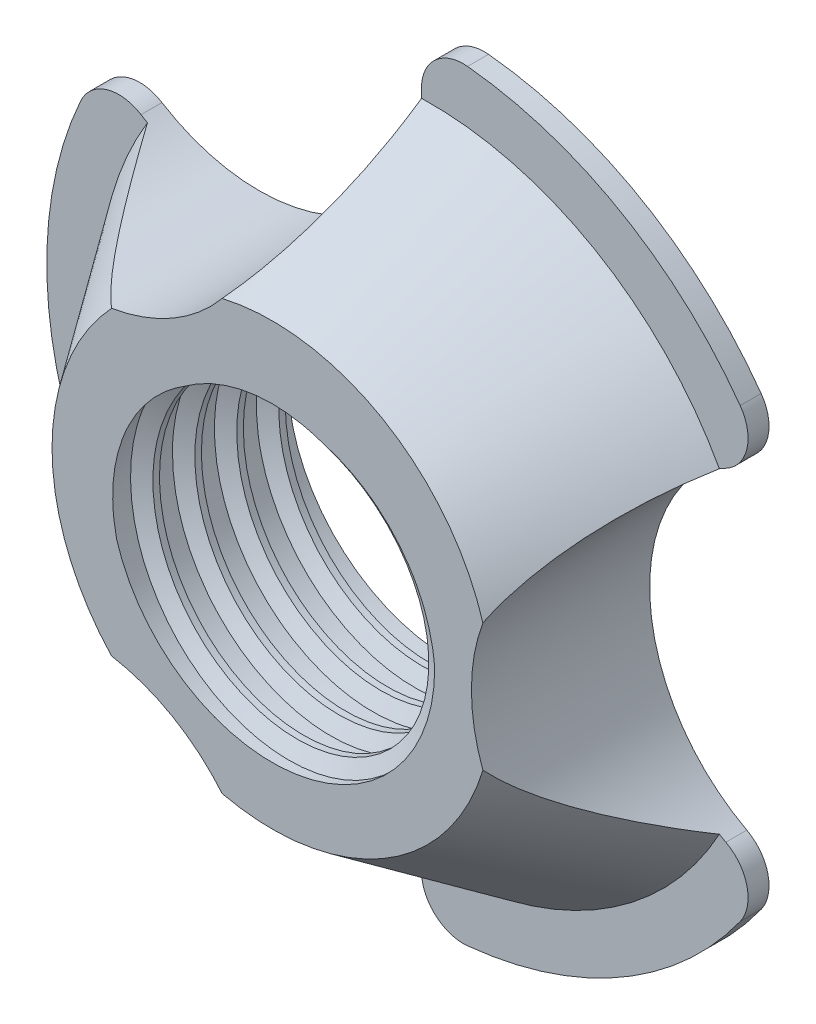
SolidWorks part; units mm, degrees
ref_plane "Спереди" through (0, 0, 0) normal (0, 0, 1) x (1, 0, 0)
ref_plane "Сверху" through (0, 0, 0) normal (0, 1, 0) x (1, 0, 0)
ref_plane "Справа" through (0, 0, 0) normal (1, 0, 0) x (0, 0, -1)
sketch "Эскиз2" plane through (0, 0, 0) normal (0, 0, 1) x (1, 0, 0)
  circle A2 centre (0, 0) radius 21
  dimension "D1" = 42
extrude "Бобышка-Вытянуть2" add sketch "Эскиз2" against normal blind 15 draft 35 separate body draft outward yes
sketch "Эскиз6" plane through (0, 0, -15) normal (0, 0, -1) x (-1, 0, 0)
  circle A0 centre (0, 0) radius 31.5031 construction
  circle A2 centre (0, 0) radius 36.5031
  dimension "D1" = 5
extrude "Бобышка-Вытянуть3" add sketch "Эскиз6" along normal blind 2
sketch "Эскиз7" plane through (0, 0, -17) normal (0, 0, -1) x (-1, 0, 0)
  circle A1 centre (0, 0) radius 31.5031 construction
  circle A2 centre (0, 0) radius 31.5031 construction
  circle A3 centre (-36.5031, 0) radius 17.5
  circle A4 centre (18.2516, 31.6126) radius 17.5
  circle A5 centre (18.2516, -31.6126) radius 17.5
  circle A6 centre (0, 0) radius 36.5031 construction
  point P12 (0, 0)
  dimension "D1" = 35
  dimension "D2" = 3
extrude "Вырез-Вытянуть1" cut sketch "Эскиз7" against normal through all
fillet "Скругление1" radius 4 6 edges at (32.3083, -16.9898, -16) (-1.4405, -36.4747, -16) (-30.8677, -19.4849, -16) (-30.8677, 19.4849, -16) (-1.4405, 36.4747, -16) (32.3083, 16.9898, -16)
sketch "Эскиз9" plane through (0, 0, 0) normal (0, 0, 1) x (1, 0, 0)
  circle A2 centre (0, 0) radius 15.5
  dimension "D1" = 31
extrude "Вырез-Вытянуть2" cut sketch "Эскиз9" against normal through all
thread "Резьба1" pitch 2.5 method extrude trim with start face yes trim with end face yes profile "Профиль резьбы1" start angle 0, offset 10, length 0, pitch 4, diameter 31
ref_plane "Плоскость1" through (-15.5, 0, 10) normal (0, -1, 0) x (-1, 0, 0)
sketch "Профиль резьбы1" plane through (-15.5, 0, 10) normal (0, -1, 0) x (-1, 0, 0)
  line L0 (0, 0) -> (0, 2.5) construction
  line L11 (0, 0) -> (0, 2.1875)
  line L12 (0, 2.1875) -> (-1.3532, 1.4062)
  line L13 (-1.3532, 1.4062) -> (-1.3532, 0.7812)
  line L15 (-1.3532, 0.7812) -> (0, 0)
  line L17 (-1.3532, 1.0937) -> (0, 1.0937) construction
  point P2 (0, 0)
  dimension "Pitch" = 2.5
  dimension "Profile_Angle" = 60
  dimension "Profile_Land" = 0.625
  dimension "Profile_Height" = 1.3532
